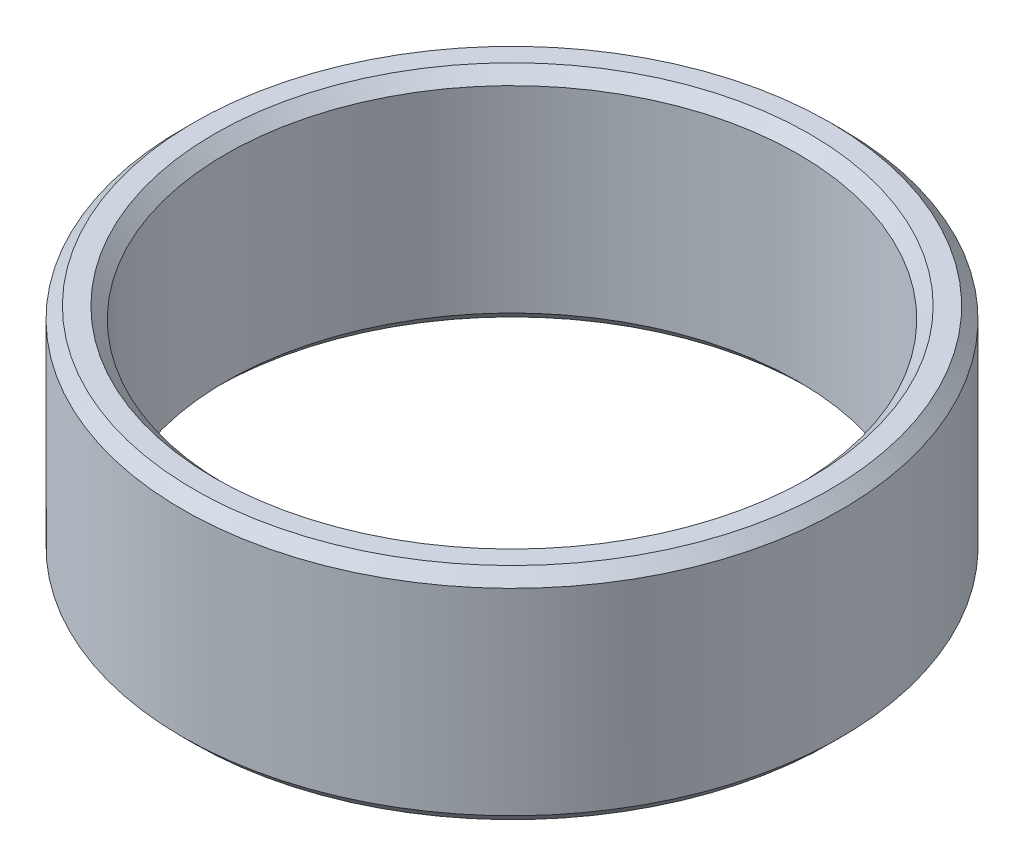
SolidWorks part; units mm, degrees
ref_plane "Front Plane" through (0, 0, 0) normal (0, 0, 1) x (1, 0, 0)
ref_plane "Top Plane" through (0, 0, 0) normal (0, 1, 0) x (1, 0, 0)
ref_plane "Right Plane" through (0, 0, 0) normal (1, 0, 0) x (0, 0, -1)
sketch "Sketch1" plane through (0, 0, 0) normal (0, 1, 0) x (1, 0, 0)
  circle A0 centre (0, 0) radius 42.5
  dimension "SLEEVE_OD" = 85
extrude "Boss-Extrude1" add sketch "Sketch1" along normal blind 28.3842
sketch "Sketch2" plane through (0, 0, 0) normal (0, 1, 0) x (1, 0, 0)
  circle A0 centre (0, 0) radius 36.9129
  dimension "BORE_D" = 73.8258
extrude "Cut-Extrude1" cut sketch "Sketch2" along normal through all
chamfer "Chamfer1" distance 1.4943 angle 45 4 edges at (0, 28.3842, 36.9129) (0, 0, 36.9129) (0, 0, 42.5) (0, 28.3842, 42.5)
